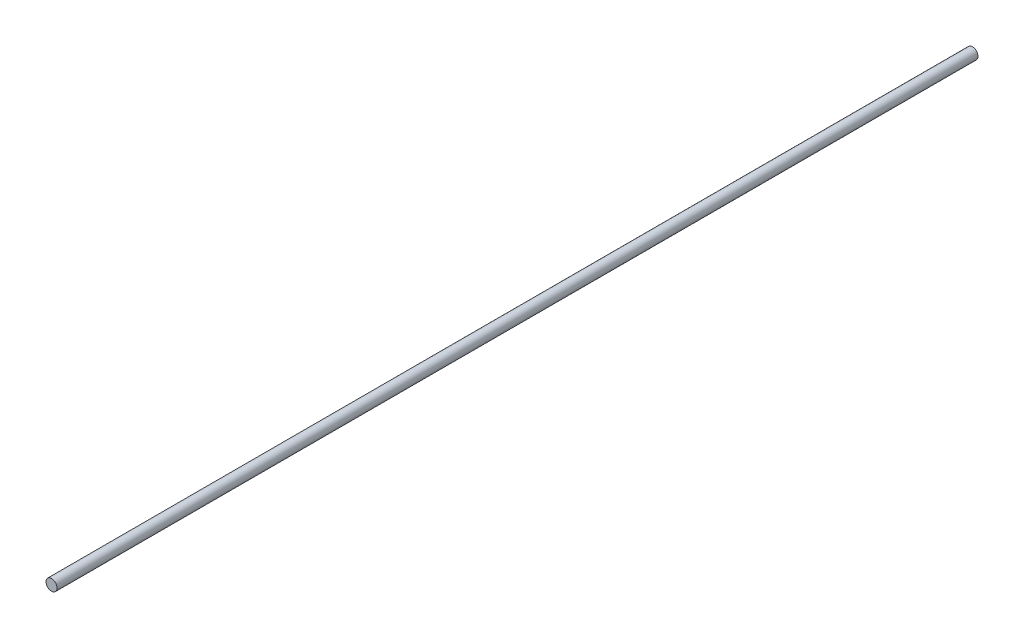
SolidWorks part; units mm, degrees
material "ABS"
ref_plane "Plan de face" through (0, 0, 0) normal (0, 0, 1) x (1, 0, 0)
ref_plane "Plan de dessus" through (0, 0, 0) normal (0, 1, 0) x (1, 0, 0)
ref_plane "Plan de droite" through (0, 0, 0) normal (1, 0, 0) x (0, 0, -1)
sketch "Esquisse1" plane through (0, 0, 0) normal (0, 0, 1) x (1, 0, 0)
  circle A0 centre (0, 0) radius 1.5
  dimension "D1" = 3
extrude "Boss.-Extru.1" add sketch "Esquisse1" along normal blind 125 and the other way blind 125
